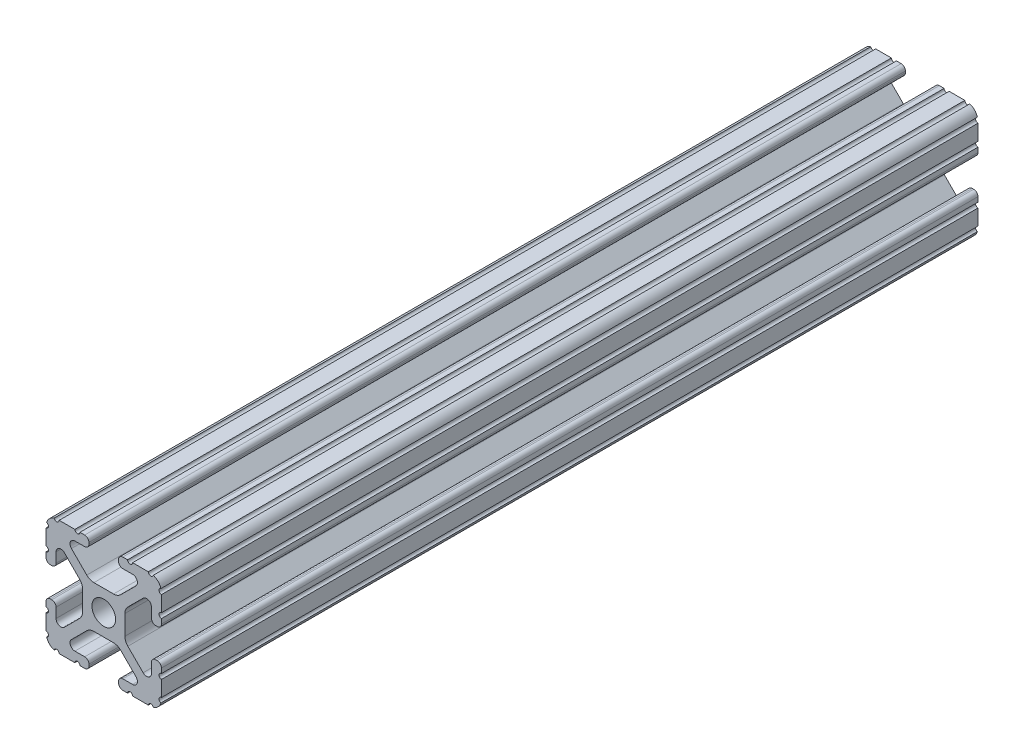
SolidWorks part; units mm, degrees
ref_plane "Front Plane" through (0, 0, 0) normal (0, 0, 1) x (1, 0, 0)
ref_plane "Top Plane" through (0, 0, 0) normal (0, 1, 0) x (1, 0, 0)
ref_plane "Right Plane" through (0, 0, 0) normal (1, 0, 0) x (0, 0, -1)
sketch "Sketch2" plane through (0, 0, 0) normal (0, 0, 1) x (1, 0, 0)
  line L0 (0, 12.7) -> (0, -12.7) construction
  line L1 (-12.7, 0) -> (12.7, 0) construction
  line L2 (3.2512, -12.7) -> (12.7, -12.7)
  line L3 (12.7, -12.7) -> (12.7, -3.2512)
  line L4 (3.2512, -12.7) -> (3.2512, -10.4902)
  line L5 (3.2512, -10.4902) -> (8.9276, -10.4902)
  line L6 (8.9276, -10.4902) -> (3.0856, -4.6482)
  line L7 (0, 0) -> (12.7, -12.7) construction
  line L8 (12.7, -3.2512) -> (10.4902, -3.2512)
  line L9 (10.4902, -3.2512) -> (10.4902, -8.9276)
  line L10 (10.4902, -8.9276) -> (4.6482, -3.0856)
  circle A0 centre (0, 0) radius 2.6035
  arc A1 (6.3485, -10.4902) -> (7.1039, -8.6665) centre (6.3485, -9.4219) ccw construction
  point P8 (0, -4.6482)
  dimension "Center Hole Diameter" = 5.207
  dimension "Rail Height" = 25.4
  dimension "Rail Width" = 25.4
  dimension "T-Slot Width" = 6.5024
  dimension "Slot Inner Width" = 14.8336
  dimension "Thickness" = 2.2098
  dimension "Slot Depth" = 5.842
  dimension "D1" = 2.2098
sketch "Sketch3" plane through (0, 0, 0) normal (1, 0, 0) x (0, 0, -1)
  line L0 (-89.7887, -12.7) -> (89.7887, -12.7) construction
  line L1 (-64.3887, 0) -> (64.3887, 0) construction
  line L2 (89.7887, 0) -> (-89.7887, 0) construction
sketch "Sketch4" plane through (0, 0, 0) normal (0, 0, 1) x (1, 0, 0)
  line L0 (4.1904, -12.7) -> (10.1173, -12.7)
  line L1 (3.2512, -12.7) -> (12.7, -12.7) construction
  line L2 (3.2512, -12.7) -> (3.2512, -10.4902) construction
  line L3 (3.2512, -10.4902) -> (8.9276, -10.4902) construction
  line L4 (3.2512, -11.4294) -> (3.2512, -11.7608)
  line L5 (4.1904, -10.4902) -> (6.3485, -10.4902)
  line L6 (0, -4.6482) -> (2.164, -4.6482)
  line L7 (8.9276, -10.4902) -> (3.0856, -4.6482) construction
  line L8 (3.7373, -5.2999) -> (7.1039, -8.6665)
  line L9 (12.7, -12.7) -> (12.7, -3.2512) construction
  line L10 (10.4902, -8.9276) -> (4.6482, -3.0856) construction
  line L11 (10.4902, -3.2512) -> (10.4902, -8.9276) construction
  line L12 (10.4902, -6.3485) -> (10.4902, -4.1904)
  line L13 (12.7, -3.2512) -> (10.4902, -3.2512) construction
  line L14 (11.4294, -3.2512) -> (11.7608, -3.2512)
  line L15 (12.7, -4.1904) -> (12.7, -10.1173)
  line L16 (8.6665, -7.1039) -> (5.2999, -3.7373)
  line L17 (4.6482, 0) -> (4.6482, -2.164)
  line L18 (-12.7, 0) -> (12.7, 0) construction
  line L19 (0, -4.6482) -> (0, -2.6035)
  line L20 (0, 12.7) -> (0, -12.7) construction
  line L21 (4.6482, 0) -> (2.6035, 0)
  arc A0 (3.2512, -11.7608) -> (4.1904, -12.7) centre (4.1904, -11.7608) ccw
  arc A2 (3.2512, -11.4294) -> (4.1904, -10.4902) centre (4.1904, -11.4294) cw
  arc A3 (6.3485, -10.4902) -> (7.1039, -8.6665) centre (6.3485, -9.4219) ccw
  arc A4 (2.164, -4.6482) -> (3.7373, -5.2999) centre (2.164, -6.8732) cw
  arc A5 (10.1173, -12.7) -> (12.7, -10.1173) centre (10.1173, -10.1173) ccw
  arc A6 (8.6665, -7.1039) -> (10.4902, -6.3485) centre (9.4219, -6.3485) ccw
  arc A7 (10.4902, -4.1904) -> (11.4294, -3.2512) centre (11.4294, -4.1904) cw
  arc A8 (11.7608, -3.2512) -> (12.7, -4.1904) centre (11.7608, -4.1904) cw
  arc A9 (5.2999, -3.7373) -> (4.6482, -2.164) centre (6.8732, -2.164) cw
  circle A10 centre (0, 0) radius 2.6035 construction
  arc A11 (0, -2.6035) -> (2.6035, 0) centre (0, 0) ccw
  dimension "D1" = 2.5827
  dimension "D2" = 2.225
  dimension "D3" = 0.9392
extrude "Boss-Extrude1" add sketch "Sketch4" along normal up to vertex (89.7887 mm away) from vertex up to point (0, -12.7, 89.7887) starting at point (0, -12.7, -89.7887)
sketch "Sketch5" plane through (0, 0, 0) normal (0, 0, 1) x (1, 0, 0)
  line L0 (3.2512, -12.7) -> (12.7, -12.7) construction
  line L1 (4.1904, -10.4902) -> (6.3485, -10.4902) construction
  line L3 (0, 0) -> (12.7, -12.7) construction
  line L4 (6.3485, -10.4902) -> (6.3485, -12.7) construction
  line L5 (8.9276, -10.4902) -> (3.0856, -4.6482) construction
  circle A0 centre (10.3562, -12.7) radius 0.5524
  circle A1 centre (5.796, -12.7) radius 0.5524
  circle A2 centre (12.7, -10.3562) radius 0.5524
  circle A3 centre (12.7, -5.796) radius 0.5524
  point P10 (5.2694, -10.4902)
  point P12 (9.4219, -6.3485)
  dimension "D1" = 1.1049
extrude "Cut-Extrude1" cut sketch "Sketch5" against normal through all both and the other way through all
mirror "Mirror1" about plane through (0, 0, 0) normal (1, 0, 0) of bodies 137 134
mirror "Mirror2" about plane through (0, 0, 0) normal (0, 1, 0) of bodies 135
equation "\"D1@Sketch2\"=\"Thickness@Sketch2\""
equation "\"D2@Sketch4\"=\"Slot Inner Width@Sketch2\"*0.15"
equation "\"D1@Sketch4\"=\"D3@Sketch4\"*2.75"
equation "\"D3@Sketch4\"=\"Thickness@Sketch2\"*0.425"
equation "\"D1@Sketch5\"=\"Thickness@Sketch2\"*0.5"
equation "\"D1@Boss-Extrude1\"=\"Length@Sketch3\""
